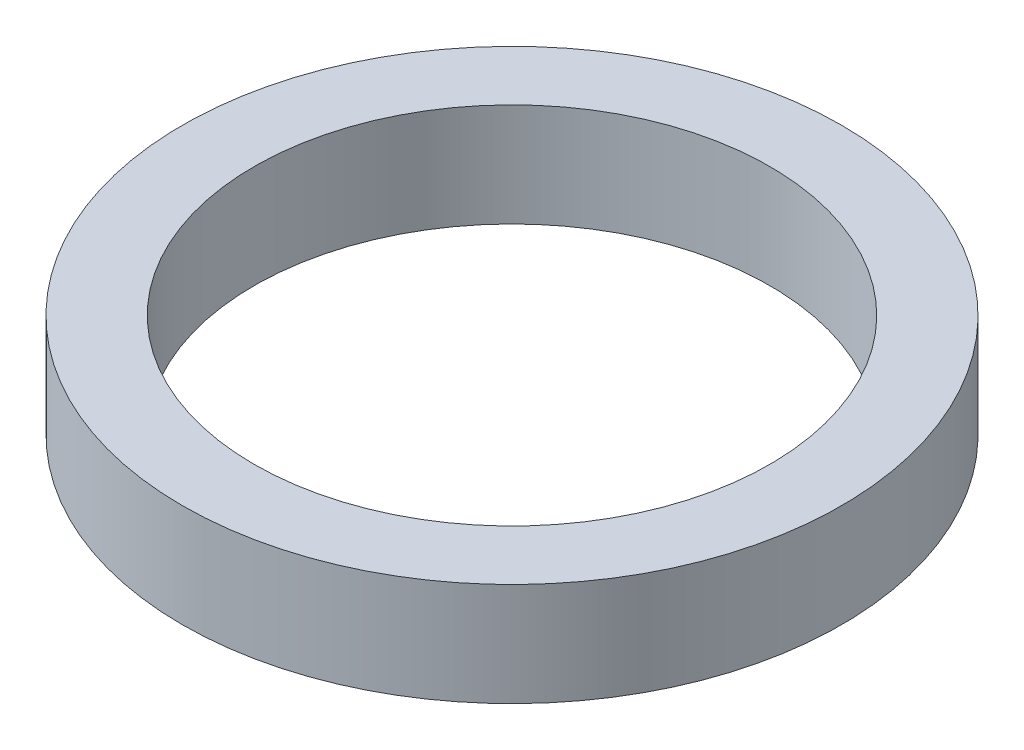
SolidWorks part; units mm, degrees
ref_plane "Front Plane" through (0, 0, 0) normal (0, 0, 1) x (1, 0, 0)
ref_plane "Top Plane" through (0, 0, 0) normal (0, 1, 0) x (1, 0, 0)
ref_plane "Right Plane" through (0, 0, 0) normal (1, 0, 0) x (0, 0, -1)
sketch "Sketch1" plane through (0, 0, 0) normal (0, 1, 0) x (1, 0, 0)
  circle A0 centre (0, 0) radius 57.5
  dimension "FLANGE_OD" = 115
extrude "Boss-Extrude1" add sketch "Sketch1" along normal blind 18
sketch "Sketch2" plane through (0, 0, 0) normal (0, 1, 0) x (1, 0, 0)
  circle A0 centre (0, 0) radius 45
  dimension "BORE_D" = 90
extrude "Cut-Extrude1" cut sketch "Sketch2" along normal through all
sketch "Sketch3" plane through (0, 18, 0) normal (0, 1, 0) x (1, 0, 0)
  circle A0 centre (0, 0) radius 24.7834 construction
  circle A1 centre (-24.7834, 0) radius 2.1736
  dimension "BOLT_D" = 4.3473
  dimension "BOLT_PCD" = 49.5668
extrude "Cut-Extrude2" cut sketch "Sketch3" against normal blind 16.6185 rebuild error yes
pattern_circular "CirPattern1" count 3 over 360 rebuild error yes
